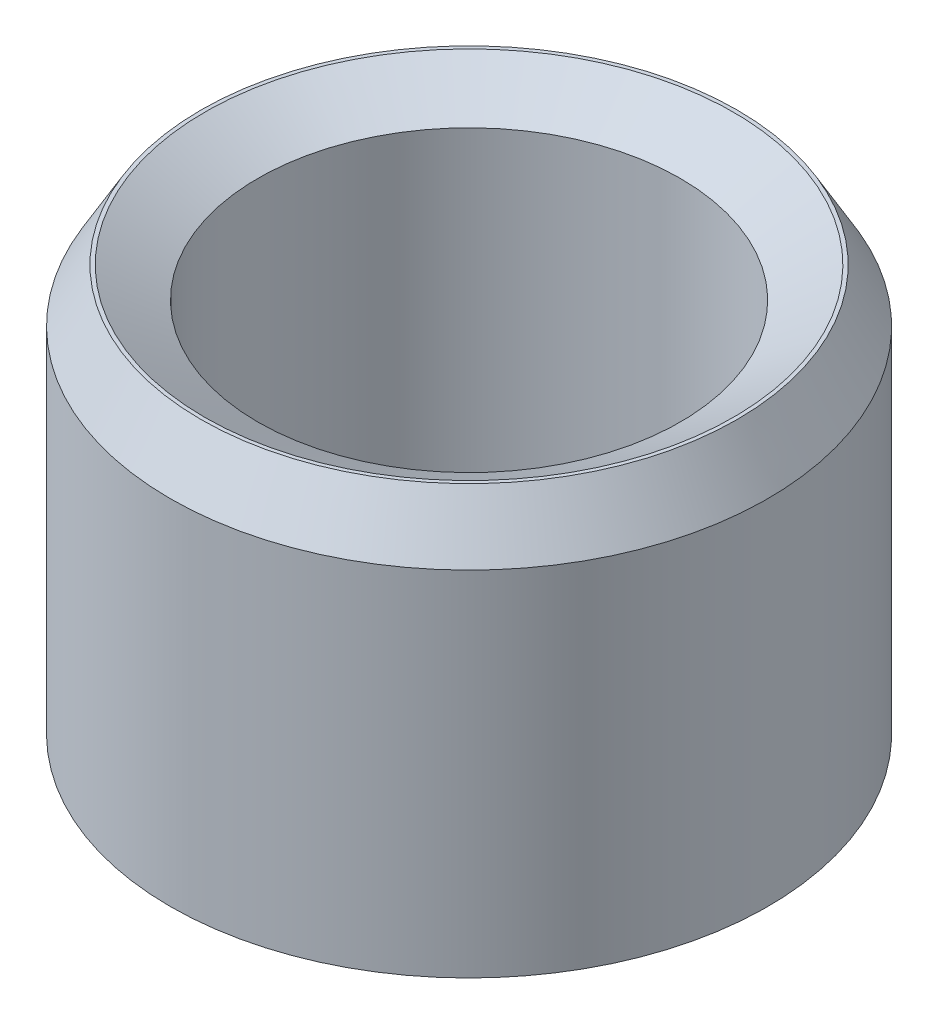
SolidWorks part; units mm, degrees
ref_plane "Front Plane" through (0, 0, 0) normal (0, 0, 1) x (1, 0, 0)
ref_plane "Top Plane" through (0, 0, 0) normal (0, 1, 0) x (1, 0, 0)
ref_plane "Right Plane" through (0, 0, 0) normal (1, 0, 0) x (0, 0, -1)
sketch "Sketch1" plane through (0, 0, 0) normal (0, 1, 0) x (1, 0, 0)
  circle A0 centre (0, 0) radius 12.5
  dimension "SLEEVE_OD" = 25
extrude "Boss-Extrude1" add sketch "Sketch1" along normal blind 18.2873
sketch "Sketch2" plane through (0, 0, 0) normal (0, 1, 0) x (1, 0, 0)
  circle A0 centre (0, 0) radius 8.8335
  dimension "BORE_D" = 17.667
extrude "Cut-Extrude1" cut sketch "Sketch2" along normal through all
chamfer "Chamfer1" distance 2.2253 angle 30 4 edges at (0, 18.2873, 8.8335) (0, 0, 8.8335) (0, 0, 12.5) (0, 18.2873, 12.5) first distance on face at (0, 18.2873, 8.8335) first distance on face at (0, 0, 8.8335) first distance on face at (0, 18.2873, 12.5)
